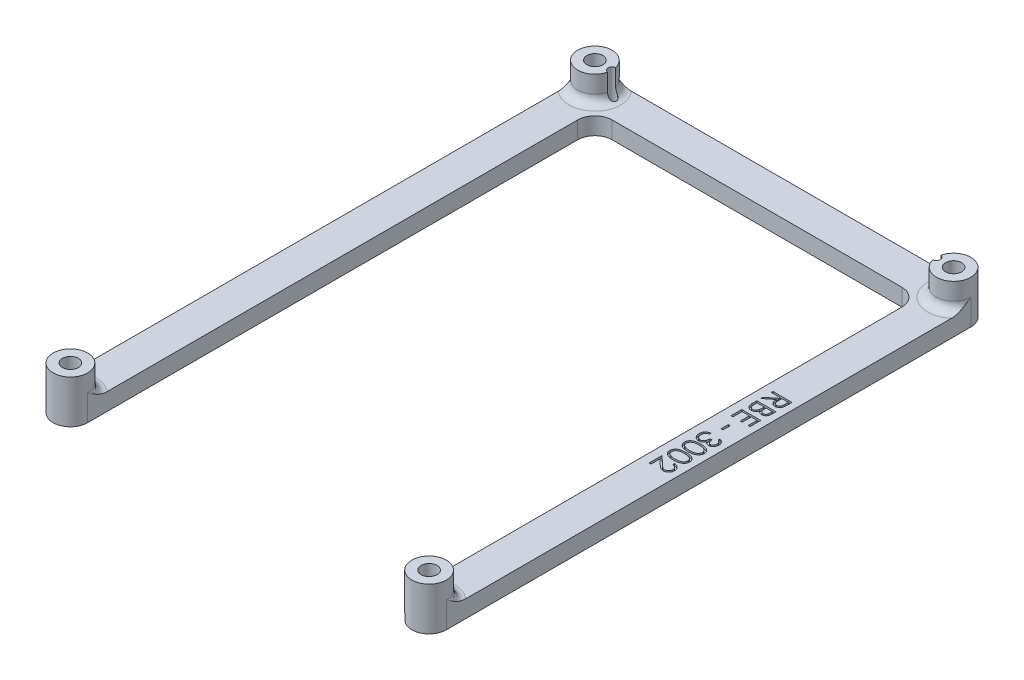
SolidWorks part; units mm, degrees
ref_plane "Front Plane" through (0, 0, 0) normal (0, 0, 1) x (1, 0, 0)
ref_plane "Top Plane" through (0, 0, 0) normal (0, 1, 0) x (1, 0, 0)
ref_plane "Right Plane" through (0, 0, 0) normal (1, 0, 0) x (0, 0, -1)
sketch "Sketch1" plane through (0, 0, 0) normal (0, 1, 0) x (1, 0, 0)
  line L0 (-36.175, 51.425) -> (36.175, 51.425)
  line L1 (-33, -48.25) -> (-29.825, -48.25) construction
  line L2 (-33, -48.25) -> (-33, 48.25) construction
  line L3 (-33, 48.25) -> (33, 48.25) construction
  line L4 (33, -48.25) -> (33, 48.25) construction
  line L5 (-33, -48.25) -> (-29.825, -43.6078) construction
  line L6 (-33, 48.25) -> (30.8285, -45.075) construction
  line L7 (36.175, -51.425) -> (36.175, 51.425)
  line L8 (-36.175, -51.425) -> (-29.825, -51.425)
  line L9 (-36.175, -51.425) -> (-36.175, 51.425)
  line L10 (-29.825, 45.075) -> (29.825, 45.075)
  line L11 (29.825, -45.075) -> (29.825, 45.075)
  line L12 (-29.825, -45.075) -> (-30.8285, -45.075) construction
  line L13 (-29.825, -45.075) -> (-29.825, 45.075)
  line L14 (-29.825, -45.075) -> (-29.825, -51.425)
  line L15 (29.825, -45.075) -> (29.825, -51.425)
  line L16 (-30.8285, -45.075) -> (30.8285, -45.075) construction
  line L17 (30.8285, -45.075) -> (29.825, -45.075) construction
  line L18 (-29.825, -45.075) -> (29.825, -45.075) construction
  line L19 (-29.825, -48.25) -> (29.825, -48.25) construction
  line L20 (29.825, -48.25) -> (33, -48.25) construction
  line L21 (-33, -48.25) -> (33, -48.25) construction
  line L22 (-29.825, -51.425) -> (29.825, -51.425) construction
  line L23 (29.825, -51.425) -> (36.175, -51.425)
  line L24 (-36.175, -51.425) -> (36.175, -51.425) construction
  line L25 (-30.8285, -45.075) -> (0, 0) construction
  line L26 (0, 0) -> (33, 48.25) construction
  line L27 (-29.825, -43.6078) -> (-30.8285, -45.075) construction
  line L28 (30.8285, -45.075) -> (29.825, -43.6078) construction
  line L29 (29.825, -43.6078) -> (33, -48.25) construction
  circle A0 centre (-33, 48.25) radius 1.475
  circle A1 centre (33, 48.25) radius 1.475
  circle A2 centre (33, -48.25) radius 1.475
  circle A3 centre (-33, -48.25) radius 1.475
  point P0 (0, 0)
  dimension "D3" = 2.95
  dimension "D1" = 66
  dimension "D2" = 96.5
  dimension "D4" = 3.175
  dimension "D5" = 3.175
extrude "Boss-Extrude1" add sketch "Sketch1" along normal blind 3.175
fillet "Fillet1" radius 3.175 8 edges at (29.825, 1.5875, -45.075) (-29.825, 1.5875, -45.075) (-36.175, 1.5875, -51.425) (36.175, 1.5875, -51.425) (-36.175, 1.5875, 51.425) (36.175, 1.5875, 51.425) (29.825, 1.5875, 51.425) (-29.825, 1.5875, 51.425)
sketch "Sketch2" plane through (0, 3.175, 0) normal (0, 1, 0) x (1, 0, 0)
  circle A0 centre (-33, 48.25) radius 1.475 construction
  circle A1 centre (-33, 48.25) radius 1.475
  circle A2 centre (-33, 48.25) radius 3.175
  arc A3 (-33, 51.425) -> (-36.175, 48.25) centre (-33, 48.25) ccw construction
extrude "Boss-Extrude2" add sketch "Sketch2" along normal blind 4.7625
mirror "Mirror3" about plane through (0, 0, 0) normal (1, 0, 0) of "Boss-Extrude2"
mirror "Mirror4" about plane through (0, 0, 0) normal (0, 0, 1) of "Mirror3", "Boss-Extrude2"
fillet "Fillet2" radius 1.5875 4 edges at (-30.7549, 3.175, -46.0049) (-33, 3.175, 45.075) (30.7549, 3.175, -46.0049) (33, 3.175, 45.075)
sketch "Sketch3" plane through (0, 3.175, 0) normal (0, 1, 0) x (1, 0, 0)
  line L0 (-29.8, 48.25) -> (29.8, 48.25) construction
  line L1 (0, 51.425) -> (0, 45.075) construction
  line L2 (29.4502, 51.425) -> (-29.4502, 51.425) construction
  line L3 (-26.65, 45.075) -> (26.65, 45.075) construction
  circle A0 centre (29.8, 48.25) radius 0.75
  circle A1 centre (-29.8, 48.25) radius 0.75
  point P10 (0, 48.25)
  point P11 (0, 48.25)
  dimension "D2" = 1.5
  dimension "D1" = 59.6
extrude "Cut-Extrude1" cut sketch "Sketch3" against normal through all both and the other way through all
sketch "Sketch4" plane through (0, 3.175, 0) normal (0, 1, 0) x (1, 0, 0)
  line L0 (31.414, 17.0568) -> (31.414, -18.5101) construction
  text T0 "RBE - 3002"
extrude "Cut-Extrude2" cut sketch "Sketch4" against normal blind 0.4
